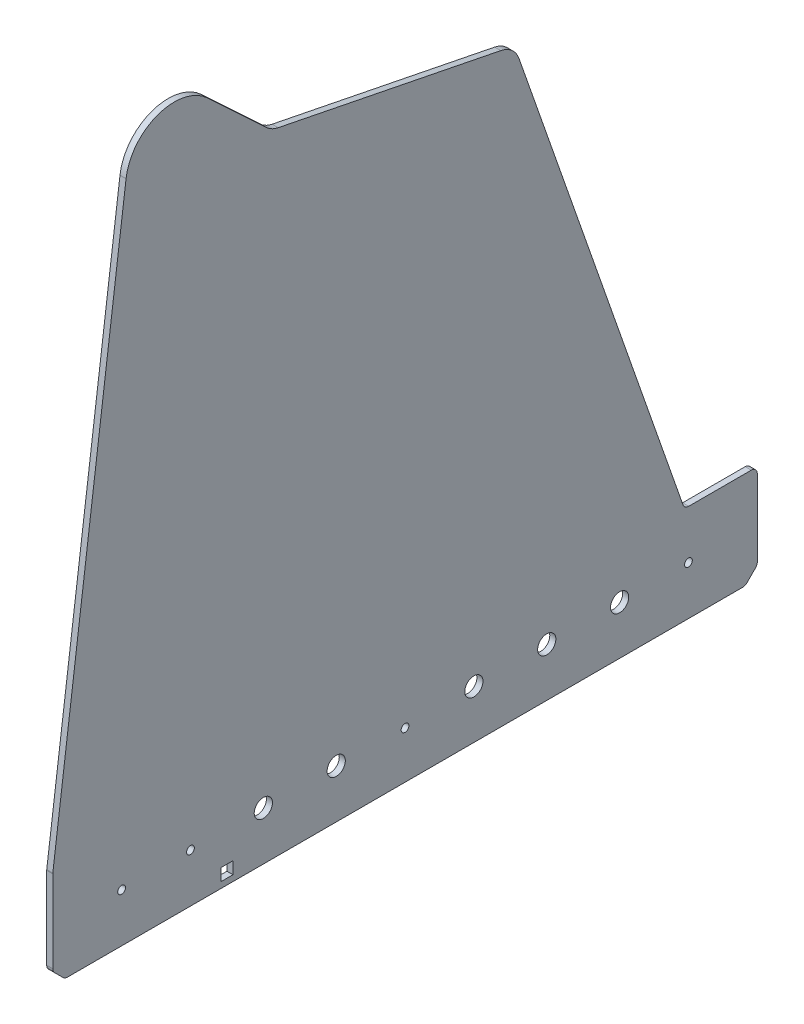
SolidWorks part; units mm, degrees
ref_plane "Front Plane" through (0, 0, 0) normal (0, 0, 1) x (1, 0, 0)
ref_plane "Top Plane" through (0, 0, 0) normal (0, 1, 0) x (1, 0, 0)
ref_plane "Right Plane" through (0, 0, 0) normal (1, 0, 0) x (0, 0, -1)
sketch "Sketch1" plane through (0, 0, 0) normal (1, 0, 0) x (0, 0, -1)
  line L0 (-184.15, -24.6062) -> (184.15, -24.6062)
  line L1 (184.15, -24.6062) -> (184.15, 26.1938)
  line L2 (184.15, 26.1938) -> (146.05, 26.1937)
  line L3 (146.05, 26.1937) -> (57.15, 280.1938)
  line L5 (-145.839, 321.5609) -> (-184.15, 26.1938)
  line L6 (-184.15, 26.1938) -> (-184.15, -24.6062)
  line L7 (-184.15, 350.0437) -> (184.15, 350.0437) construction
  line L8 (57.15, 280.1938) -> (-69.85, 305.5938)
  line L9 (-69.85, 305.5938) -> (-103.3099, 336.854)
  arc A0 (-103.3099, 336.854) -> (-145.839, 321.5609) centre (-120.65, 318.2937) ccw
  point P8 (0, -24.6062)
  dimension "D1" = 368.3
  dimension "D7" = 25.4
  dimension "D2" = 50.8
  dimension "D3" = 38.1
  dimension "D4" = 24.6062
  dimension "D5" = 374.65
  dimension "D6" = 304.8
  dimension "D8" = 342.9
  dimension "D9" = 127
  dimension "D10" = 304.8
  dimension "D11" = 25.4
  dimension "D12" = 127
extrude "Boss-Extrude1" add sketch "Sketch1" along normal blind 3.175
chamfer "Chamfer1" distance 6.35 angle 45 2 edges at (1.5875, -24.6062, 184.15) (1.5875, -24.6062, -184.15)
fillet "Fillet1" radius 12.7 2 edges at (1.5875, 305.5938, 69.85) (1.5875, 280.1938, -57.15)
fillet "Fillet2" radius 3.175 3 edges at (1.5875, 26.1938, 184.15) (1.5875, 26.1938, -184.15) (1.5875, 26.1937, -146.05)
fillet "Fillet3" radius 3.175 4 edges at (1.5875, -18.2563, -184.15) (1.5875, -24.6062, -177.8) (1.5875, -18.2562, 184.15) (1.5875, -24.6062, 177.8)
sketch "Sketch16" plane through (3.175, 0, 0) normal (1, 0, 0) x (0, 0, -1)
  circle A0 centre (112.1746, 0.7937) radius 4.7625
  circle A1 centre (74.0746, 0.7937) radius 4.7625
  circle A2 centre (35.9746, 0.7937) radius 4.7625
  circle A3 centre (-35.9746, 0.7938) radius 4.7625
  circle A4 centre (-74.0746, 0.7938) radius 4.7625
  point P24 (-149.8601, 7.21)
  point P25 (-74.0746, 0.7938)
  dimension "D1" = 9.525
extrude "Cut-Extrude1" cut sketch "Sketch16" against normal up to next
sketch "Sketch21" plane through (3.175, 0, 0) normal (1, 0, 0) x (0, 0, -1)
  circle A0 centre (-148.1579, 0.7937) radius 2.032
  circle A1 centre (-112.1746, 0.7937) radius 2.032
  circle A2 centre (0, 0) radius 2.032
  circle A3 centre (148.1579, 0.7938) radius 2.032
  dimension "D1" = 4.064
extrude "Cut-Extrude2" cut sketch "Sketch21" against normal up to next
sketch "Sketch22" plane through (3.175, 0, 0) normal (1, 0, 0) x (0, 0, -1)
  line L0 (-96.2996, -15.1473) -> (-89.9496, -15.1473) construction
  line L1 (-96.2996, -15.1473) -> (-89.9496, -15.1473)
  line L2 (-96.2996, -15.1473) -> (-96.2996, -21.4973)
  line L3 (-96.2996, -21.4973) -> (-89.9496, -21.4973)
  line L4 (-89.9496, -15.1473) -> (-89.9496, -21.4973)
  line L5 (-96.2996, -15.1473) -> (-89.9496, -21.4973) construction
  line L6 (-96.2996, -21.4973) -> (-89.9496, -15.1473) construction
  line L7 (-89.9496, -15.1473) -> (-89.9496, -19.8734) construction
  point P0 (-93.1246, -18.3223)
  point P6 (-93.8073, -19.3962)
  dimension "D1" = 6.35
extrude "Cut-Extrude3" cut sketch "Sketch22" against normal up to next
